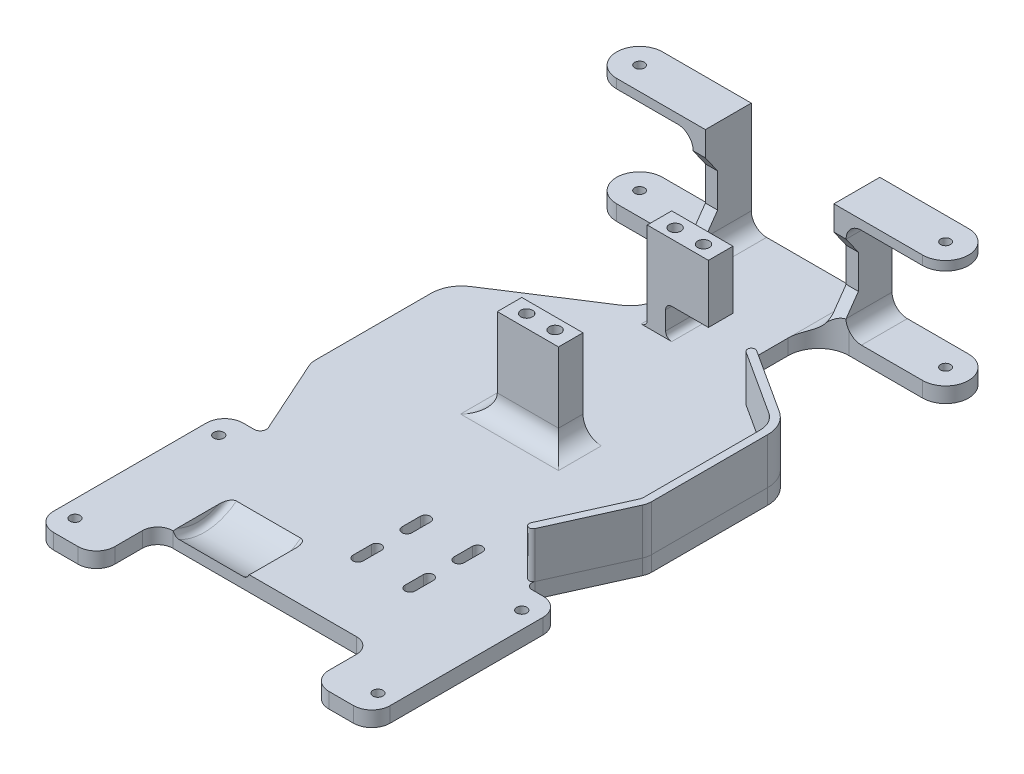
SolidWorks part; units mm, degrees
ref_plane "Front Plane" through (0, 0, 0) normal (0, 0, 1) x (1, 0, 0)
ref_plane "Top Plane" through (0, 0, 0) normal (0, 1, 0) x (1, 0, 0)
ref_plane "Right Plane" through (0, 0, 0) normal (1, 0, 0) x (0, 0, -1)
sketch "Sketch1" plane through (0, 0, 0) normal (0, 1, 0) x (1, 0, 0)
  line L1 (0, 0) -> (100, 0)
  line L2 (0, 0) -> (0, 15)
  line L3 (0, 15) -> (100, 15)
  line L4 (100, 0) -> (100, 15)
  circle A0 centre (100, 7.5) radius 7.5
  circle A1 centre (0, 7.5) radius 7.5
  circle A2 centre (0, 7.5) radius 1.6
  circle A3 centre (100, 7.5) radius 1.6
  dimension "D3" = 3.2
  dimension "D1" = 100
  dimension "D2" = 15
extrude "Boss-Extrude3" add sketch "Sketch1" along normal blind 5 contours A2 L2 A1 | A2 L2 A1 | A1 L1 A0 L3 | A3 L4 A0 | A3 L4 A0 region at (50, 0, -7.5) region at (-3.3025, 0, -7.5) region at (3.3025, 0, -7.5) region at (96.6975, 0, -7.5) region at (103.3025, 0, -7.5)
sketch "Sketch2" plane through (0, 5, 0) normal (0, 1, 0) x (1, 0, 0)
  line L0 (0, 15) -> (100, 15) construction
  line L1 (25, 15) -> (29, 15)
  line L2 (25, 15) -> (25, 0)
  line L3 (25, 0) -> (29, 0)
  line L4 (29, 15) -> (29, 0)
  line L5 (0, 0) -> (100, 0) construction
  line L6 (50, 0) -> (50, 15) construction
  line L7 (75, 0) -> (71, 0)
  line L8 (71, 15) -> (71, 0)
  line L9 (75, 15) -> (71, 15)
  line L10 (75, 15) -> (75, 0)
  circle A0 centre (0, 7.5) radius 1.6 construction
  dimension "D2" = 25
  dimension "D1" = 4
extrude "Boss-Extrude4" add sketch "Sketch2" along normal blind 32.5
sketch "Sketch3" plane through (0, 37.5, 0) normal (0, 1, 0) x (1, 0, 0)
  line L0 (75, 0) -> (75, 15) construction
  line L1 (75, 15) -> (71, 15) construction
  line L2 (71, 15) -> (71, 0) construction
  line L3 (71, 0) -> (75, 0) construction
  line L4 (25, 15) -> (25, 0) construction
  line L5 (25, 0) -> (29, 0) construction
  line L6 (29, 0) -> (29, 15) construction
  line L7 (29, 15) -> (25, 15) construction
  line L8 (25, 0) -> (25, 15) construction
  line L9 (25, 15) -> (0, 15) construction
  line L10 (0, 0) -> (25, 0) construction
  line L11 (100, 15) -> (75, 15) construction
  line L12 (75, 15) -> (75, 0) construction
  line L13 (75, 0) -> (100, 0) construction
  line L18 (75, 0) -> (75, 15)
  line L19 (75, 15) -> (71, 15)
  line L20 (71, 15) -> (71, 0)
  line L21 (71, 0) -> (75, 0)
  line L22 (25, 15) -> (25, 0)
  line L23 (25, 0) -> (29, 0)
  line L24 (29, 0) -> (29, 15)
  line L25 (29, 15) -> (25, 15)
  line L26 (25, 0) -> (25, 15)
  line L27 (25, 15) -> (0, 15)
  line L28 (0, 0) -> (25, 0)
  line L29 (100, 15) -> (75, 15)
  line L30 (75, 15) -> (75, 0)
  line L31 (75, 0) -> (100, 0)
  arc A0 (0, 15) -> (0, 0) centre (0, 7.5) ccw construction
  arc A1 (100, 0) -> (100, 15) centre (100, 7.5) ccw construction
  arc A2 (0, 15) -> (0, 0) centre (0, 7.5) ccw
  arc A3 (100, 0) -> (100, 15) centre (100, 7.5) ccw
  circle A4 centre (0, 7.5) radius 1.6
  circle A5 centre (100, 7.5) radius 1.6
  line M18 (25, 15) -> (25, 0)
  line M19 (25, 0) -> (29, 0)
  line M20 (29, 0) -> (29, 15)
  line M21 (29, 15) -> (25, 15)
  dimension "D1" = 3.2
extrude "Boss-Extrude6" add sketch "Sketch3" along normal blind 3 contours L31 A3 L29 L18 A5 | L20 L21 L18 L19 | L27 A2 L28 A4 M18 | M21 M18 M19 M20 region at (73, 37.5, -7.5) region at (90.3226, 37.5, -7.5) region at (27, 37.5, -7.5) region at (9.6774, 37.5, -7.5)
fillet "Fillet1" radius 5 6 edges at (75, 5, -7.5) (25, 5, -7.5) (75, 37.5, -7.5) (25, 37.5, -7.5) (71, 5, -7.5) (29, 5, -7.5)
sketch "Sketch4" plane through (29, 0, 0) normal (1, 0, 0) x (0, 0, -1)
  line L0 (0, 32.5) -> (0, 10) construction
  line L1 (0, 32.5) -> (4, 32.5) construction
  line L2 (0, 32.5) -> (0, 10)
  line L3 (0, 10) -> (4, 10)
  line L4 (4, 26.7874) -> (4, 15.7126)
  line L5 (0, 10) -> (15, 10) construction
  line L6 (15, 32.5) -> (0, 32.5) construction
  line L7 (0, 32.5) -> (4, 26.7874)
  line L8 (0, 10) -> (4, 15.7126)
  dimension "D1" = 4
  dimension "D2" = 55
  dimension "D3" = 4
  dimension "D4" = 4
extrude "Cut-Extrude1" cut sketch "Sketch4" against normal blind 10 and the other way through all contours L8 L4 L7 L2
sketch "Sketch5" plane through (0, 0, 0) normal (0, -1, 0) x (1, 0, 0)
  line L0 (0, -15) -> (100, -15) construction
  line L1 (40, -15) -> (60, -15)
  line L2 (40, -15) -> (40, 80)
  line L3 (40, 80) -> (60, 80)
  line L4 (60, -15) -> (60, 80)
  point P6 (50, -15)
  point P7 (50, -15)
  dimension "D1" = 20
  dimension "D2" = 95
extrude "Boss-Extrude7" add sketch "Sketch5" against normal blind 5
sketch "Sketch6" plane through (0, 5, 0) normal (0, 1, 0) x (1, 0, 0)
  line L0 (40, -80) -> (40, 0) construction
  line L1 (40, -30) -> (60, -30) construction
  line L2 (40, -30) -> (40, -71) construction
  line L3 (40, -71) -> (60, -71) construction
  line L4 (60, -30) -> (60, -71) construction
  line L5 (60, 0) -> (60, -80) construction
  line L6 (60, 0) -> (66, 0) construction
  line L7 (40, -22) -> (60, -22)
  line L8 (40, -71) -> (60, -71)
  line L9 (40, -71) -> (40, -79)
  line L10 (40, -79) -> (60, -79)
  line L11 (60, -71) -> (60, -79)
  line L12 (40, -22) -> (40, -30)
  line L13 (40, -30) -> (60, -30)
  line L14 (60, -22) -> (60, -30)
  dimension "D1" = 41
  dimension "D2" = 30
  dimension "D3" = 8
  dimension "D4" = 8
extrude "Boss-Extrude8" add sketch "Sketch6" along normal blind 29
sketch "Sketch7" plane through (0, 34, 0) normal (0, 1, 0) x (1, 0, 0)
  line L1 (50, -71) -> (50, -69.0543) construction
  line L2 (60, -71) -> (40, -71) construction
  line L3 (60, -50.5) -> (71.2332, -50.5) construction
  line L4 (60, -30) -> (60, -71) construction
  circle A0 centre (45.35, -74.75) radius 1.9
  circle A1 centre (54.65, -74.75) radius 1.9
  circle A2 centre (54.65, -26.25) radius 1.9
  circle A3 centre (45.35, -26.25) radius 1.9
  dimension "D1" = 48.5
  dimension "D3" = 3.8
  dimension "D2" = 9.3
extrude "Cut-Extrude2" cut sketch "Sketch7" against normal blind 6
sketch "Sketch8" plane through (60, 0, 0) normal (1, 0, 0) x (0, 0, -1)
  line L1 (-30, 5) -> (-22, 5)
  line L2 (-30, 5) -> (-30, 15)
  line L3 (-30, 15) -> (-22, 15)
  line L4 (-22, 5) -> (-22, 15)
  line L5 (-22, 34) -> (-22, 5) construction
  dimension "D1" = 10
extrude "Cut-Extrude3" cut sketch "Sketch8" against normal blind 14
fillet "Fillet3" radius 6 1 edges at (43, 5, 22)
fillet "Fillet4" radius 2 1 edges at (46, 5, 23)
fillet "Fillet5" radius 2 1 edges at (46, 15, 26)
sketch "Sketch9" plane through (0, 0, 0) normal (0, -1, 0) x (1, 0, 0)
  line L0 (34, 0) -> (34, 25)
  line L1 (34, 25) -> (-5, 50.2007)
  line L2 (-5, 50.2007) -> (-5, 185)
  line L3 (-5, 185) -> (105, 185)
  line L4 (66, 0) -> (66, 25)
  line L5 (50, -15) -> (50, 185) construction
  line L6 (34, -15) -> (66, -15) construction
  line L7 (66, 25) -> (105, 50.2007)
  line L8 (105, 50.2007) -> (105, 185)
  circle A0 centre (0.5, 177.5) radius 1.65
  circle A1 centre (0.5, 130.5) radius 1.65
  circle A2 centre (58, 139.5) radius 1.65
  circle A3 centre (58, 123.5) radius 1.65
  circle A4 centre (75, 139.5) radius 1.65
  circle A5 centre (75, 123.5) radius 1.65
  circle A6 centre (99.5, 130.5) radius 1.65
  circle A7 centre (99.5, 177.5) radius 1.65
  line M1 (100, 0) -> (60, 0)
  line M2 (60, 0) -> (60, 80)
  line M3 (60, 80) -> (40, 80)
  line M4 (40, 80) -> (40, 0)
  line M5 (40, 0) -> (0, 0)
  dimension "D5" = 3.3
  dimension "D4" = 5.5
  dimension "D8" = 16
  dimension "D9" = 3.3
  dimension "D1" = 200
  dimension "D2" = 25
  dimension "D3" = 55
  dimension "D6" = 47
  dimension "D7" = 7.5
  dimension "D10" = 17
  dimension "D11" = 8
  dimension "D12" = 9
extrude "Boss-Extrude9" add sketch "Sketch9" against normal blind 5 contours L5 L4 L7 L8 L3 A6 A5 A4 A3 A2 A7 M3 M2 M1 | L5 L3 L2 L1 L0 A0 A1 M3 M5 M4 region at (22.1581, 0, 111.2532) region at (77.8913, 0, 111.165)
fillet "Fillet6" radius 10 6 edges at (34, 2.5, 0) (66, 2.5, 0) (66, 2.5, 25) (34, 2.5, 25) (-5, 2.5, 50.2007) (105, 2.5, 50.2007)
fillet "Fillet7" radius 6 2 edges at (-5, 2.5, 185) (105, 2.5, 185)
fillet "Fillet8" radius 6 3 edges at (40, 5, 75) (60, 5, 75) (50, 5, 79)
sketch "Sketch10" plane through (0, 0, 0) normal (0, -1, 0) x (1, 0, 0)
  line L0 (1, 185) -> (99, 185) construction
  line L1 (15, 185) -> (85, 185)
  line L2 (15, 185) -> (15, 170)
  line L3 (20, 165) -> (80, 165)
  line L4 (85, 185) -> (85, 170)
  arc A0 (80, 165) -> (85, 170) centre (80, 170) ccw
  arc A1 (15, 170) -> (20, 165) centre (20, 170) ccw
  point P6 (50, 185)
  point P7 (50, 185)
  point P10 (85, 165)
  dimension "D3" = 5
  dimension "D1" = 70
  dimension "D2" = 20
extrude "Cut-Extrude4" cut sketch "Sketch10" against normal blind 5
fillet "Fillet9" radius 6 2 edges at (15, 2.5, 185) (85, 2.5, 185)
sketch "Sketch11" plane through (0, 0, 0) normal (0, -1, 0) x (1, 0, 0)
  line L0 (105, 123.0636) -> (92.2946, 123.0636)
  line L1 (105, 55.645) -> (105, 179) construction
  line L2 (92.2946, 123.0636) -> (105, 94.8251)
  line L3 (105, 94.8251) -> (105, 123.0636)
  line L4 (-5, 123.0636) -> (7.7054, 123.0636)
  line L5 (-5, 55.645) -> (-5, 179) construction
  line L6 (7.7054, 123.0636) -> (-5, 94.8251)
  line L7 (-5, 94.8251) -> (-5, 123.0636)
extrude "Cut-Extrude5" cut sketch "Sketch11" against normal blind 5
fillet "Fillet10" radius 6 4 edges at (105, 2.5, 94.8251) (-5, 2.5, 94.8251) (105, 2.5, 123.0636) (-5, 2.5, 123.0636)
fillet "Fillet11" radius 2 2 edges at (7.7054, 2.5, 123.0636) (92.2946, 2.5, 123.0636)
sketch "Sketch12" plane through (-5, 0, 0) normal (-1, 0, 0) x (0, 0, 1)
  line L0 (129.0636, 5) -> (179, 5) construction
  line L2 (146.2403, 5) -> (167.2403, 5)
  arc A0 (146.2403, 5) -> (167.2403, 5) centre (156.7403, 18.3697) ccw
  dimension "D1" = 17
  dimension "D2" = 21
extrude "Cut-Extrude6" cut sketch "Sketch12" against normal blind 25 from offset 25 offset against normal yes
fillet "Fillet12" radius 2 2 edges at (20, 1.423, 155.3953) (45, 1.423, 155.3953)
fillet "Fillet13" radius 2 1 edges at (40, 5, 23)
sketch "Sketch13" plane through (0, 0, 0) normal (0, -1, 0) x (1, 0, 0)
  line L0 (58, 142.5) -> (58, 136.5) construction
  line L1 (59.65, 142.5) -> (59.65, 136.5)
  line L2 (56.35, 142.5) -> (56.35, 136.5)
  line L3 (73.35, 142.5) -> (73.35, 136.5)
  line L4 (76.65, 142.5) -> (76.65, 136.5)
  line L5 (75, 142.5) -> (75, 136.5) construction
  line L6 (73.35, 126.5) -> (73.35, 120.5)
  line L7 (76.65, 126.5) -> (76.65, 120.5)
  line L8 (75, 126.5) -> (75, 120.5) construction
  line L9 (56.35, 126.5) -> (56.35, 120.5)
  line L10 (59.65, 126.5) -> (59.65, 120.5)
  line L11 (58, 126.5) -> (58, 120.5) construction
  arc A0 (59.65, 142.5) -> (56.35, 142.5) centre (58, 142.5) ccw
  arc A1 (56.35, 136.5) -> (59.65, 136.5) centre (58, 136.5) ccw
  circle A2 centre (58, 139.5) radius 1.65 construction
  arc A3 (76.65, 142.5) -> (73.35, 142.5) centre (75, 142.5) ccw
  arc A4 (73.35, 136.5) -> (76.65, 136.5) centre (75, 136.5) ccw
  arc A5 (76.65, 126.5) -> (73.35, 126.5) centre (75, 126.5) ccw
  arc A6 (73.35, 120.5) -> (76.65, 120.5) centre (75, 120.5) ccw
  arc A7 (59.65, 126.5) -> (56.35, 126.5) centre (58, 126.5) ccw
  arc A8 (56.35, 120.5) -> (59.65, 120.5) centre (58, 120.5) ccw
  point P2 (58, 139.5)
  point P14 (75, 139.5)
  point P21 (75, 123.5)
  point P28 (58, 123.5)
  dimension "D1" = 6
  dimension "D4" = 16
  dimension "D2" = 2
  dimension "D3" = 2
extrude "Cut-Extrude7" cut sketch "Sketch13" against normal blind 15
sketch "Sketch15" plane through (0, 5, 0) normal (0, 1, 0) x (1, 0, 0)
  line L0 (93.5637, -120.243) -> (104.4717, -95.9994) construction
  line L1 (70.5727, -27.9548) -> (100.4273, -47.2459) construction
  line L2 (105, -55.645) -> (105, -93.5375) construction
  line L3 (93.5637, -120.243) -> (104.4717, -95.9994)
  line L4 (79.4295, -33.6778) -> (100.4273, -47.2459)
  line L5 (105, -55.645) -> (105, -93.5375)
  line L6 (78.0727, -35.7776) -> (99.0704, -49.3457)
  line L7 (102.5, -55.645) -> (102.5, -93.5375)
  line L8 (91.2838, -119.2172) -> (102.1918, -94.9736)
  line L11 (70.5727, -27.9548) -> (100.4273, -47.2459) construction
  line L12 (69.2159, -30.0545) -> (99.0704, -49.3457) construction
  arc A0 (104.4717, -95.9994) -> (105, -93.5375) centre (99, -93.5375) ccw construction
  arc A1 (105, -55.645) -> (100.4273, -47.2459) centre (95, -55.645) ccw construction
  arc A2 (104.4717, -95.9994) -> (105, -93.5375) centre (99, -93.5375) ccw
  arc A3 (105, -55.645) -> (100.4273, -47.2459) centre (95, -55.645) ccw
  arc A4 (102.5, -55.645) -> (99.0704, -49.3457) centre (95, -55.645) ccw
  arc A5 (102.1918, -94.9736) -> (102.5, -93.5375) centre (99, -93.5375) ccw
  arc A6 (91.2838, -119.2172) -> (93.5637, -120.243) centre (92.4238, -119.7301) ccw
  arc A7 (79.4295, -33.6778) -> (78.0727, -35.7776) centre (78.7511, -34.7277) ccw
  dimension "D1" = 2.5
extrude "Boss-Extrude10" add sketch "Sketch15" along normal blind 15 separate body
